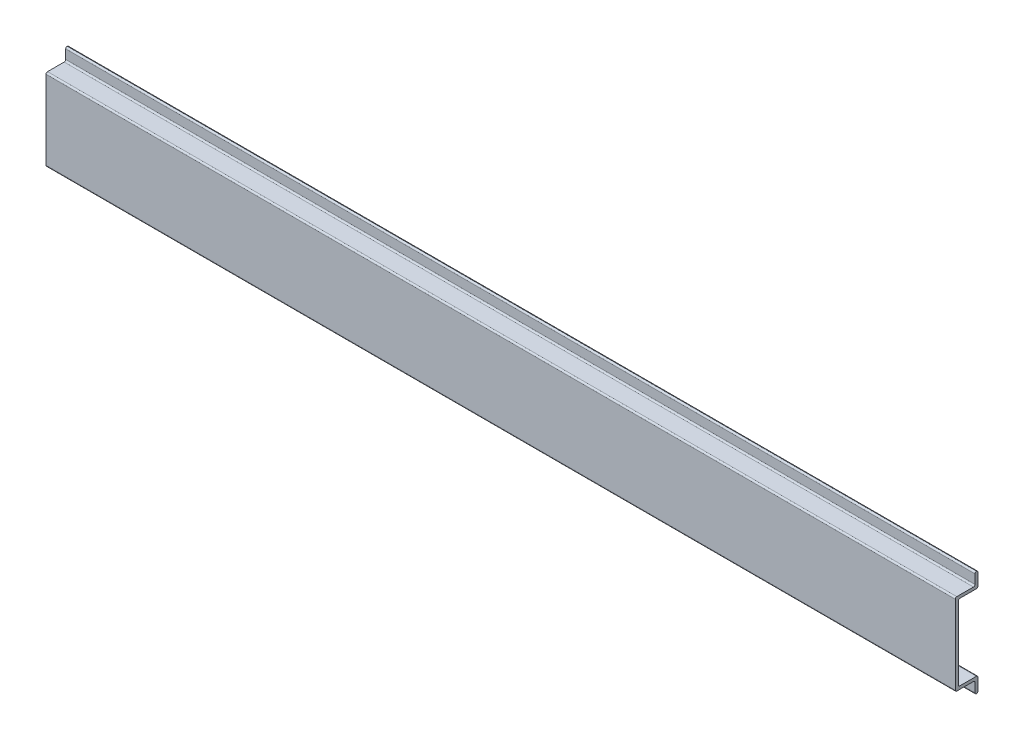
SolidWorks part; units mm, degrees
material "1.5714 (16NiCr4)"
ref_plane "Alzado" through (0, 0, 0) normal (0, 0, 1) x (1, 0, 0)
ref_plane "Planta" through (0, 0, 0) normal (0, 1, 0) x (1, 0, 0)
ref_plane "Vista lateral" through (0, 0, 0) normal (1, 0, 0) x (0, 0, -1)
sketch "Croquis1" plane through (0, 0, 0) normal (1, 0, 0) x (0, 0, -1)
  line L0 (0, 0) -> (0, 13.5)
  line L1 (0, 13.5) -> (6.5, 13.5)
  line L2 (6.5, 13.5) -> (6.5, 17.5)
  line L3 (6.5, 17.5) -> (7.5, 17.5)
  line L4 (7.5, 17.5) -> (7.5, 12.5)
  line L5 (7.5, 12.5) -> (1, 12.5)
  line L6 (1, 12.5) -> (1, -12.5)
  line L7 (1, -12.5) -> (7.5, -12.5)
  line L8 (7.5, -12.5) -> (7.5, -17.5)
  line L9 (7.5, -17.5) -> (6.5, -17.5)
  line L10 (6.5, -17.5) -> (6.5, -13.5)
  line L11 (6.5, -13.5) -> (0, -13.5)
  line L12 (0, -13.5) -> (0, 0)
  dimension "D1" = 35
  dimension "D2" = 27
  dimension "D3" = 7.5
  dimension "D4" = 1
  dimension "D5" = 1
  dimension "D6" = 1
  dimension "D7" = 1
  dimension "D8" = 1
extrude "Saliente-Extruir1" add sketch "Croquis1" along normal blind 150 and the other way blind 150
fillet "Redondeo1" radius 0.5 12 edges at (0, 12.5, -1) (0, 12.5, -7.5) (0, 17.5, -7.5) (0, 17.5, -6.5) (0, 13.5, 0) (0, 13.5, -6.5) (0, -13.5, 0) (0, -13.5, -6.5) (0, -17.5, -6.5) (0, -17.5, -7.5) (0, -12.5, -7.5) (0, -12.5, -1)
